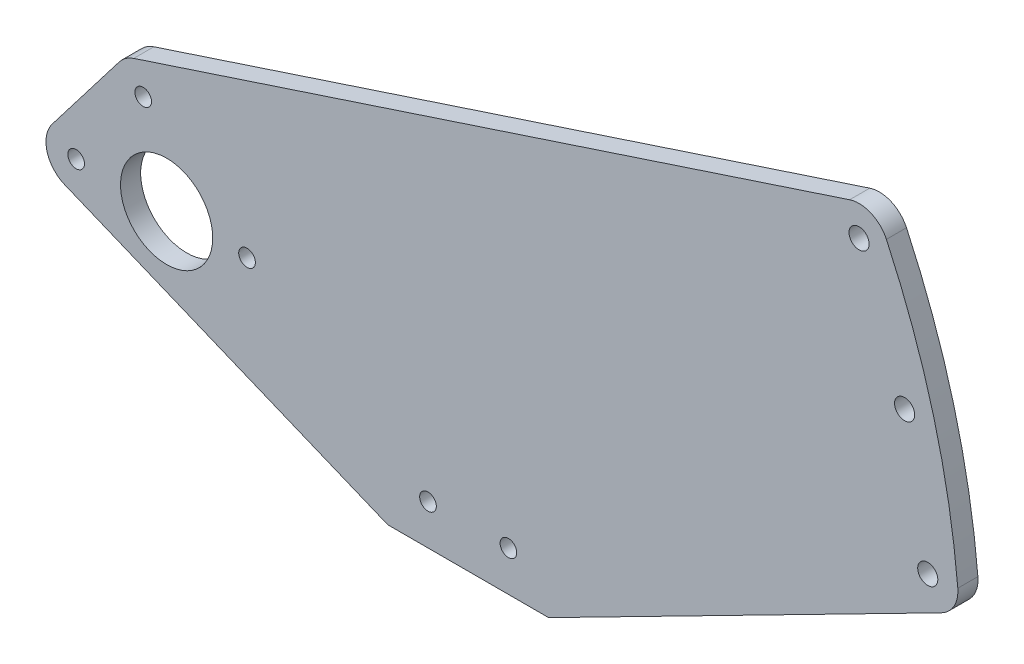
SolidWorks part; units mm, degrees
material "6061-T6 (SS)"
ref_plane "Front Plane" through (0, 0, 0) normal (0, 0, 1) x (1, 0, 0)
ref_plane "Top Plane" through (0, 0, 0) normal (0, 1, 0) x (1, 0, 0)
ref_plane "Right Plane" through (0, 0, 0) normal (1, 0, 0) x (0, 0, -1)
sketch "Sketch1" plane through (0, 0, 0) normal (0, 0, 1) x (1, 0, 0)
  line L0 (0, 0) -> (-28.575, 0) construction
  line L1 (0, 0) -> (-7.3958, 27.6013) construction
  line L2 (0, 0) -> (240.3818, 21.0307) construction
  line L3 (0, 0) -> (25.4, 0) construction
  line L4 (0, 0) -> (240.3818, 21.0307) construction
  line L5 (0, 0) -> (233.0779, 62.453) construction
  line L6 (-36.1317, 5.7985) -> (-14.9524, 33.3998)
  line L7 (-32.1995, -8.8084) -> (69.85, -50.8)
  line L8 (-10.3723, 36.6493) -> (215.7155, 111.0258)
  line L10 (0, 0) -> (0, -38.1) construction
  line L11 (0, -38.1) -> (233.0779, -38.1) construction
  line L12 (82.55, -38.1) -> (107.95, -38.1) construction
  line L13 (69.85, -50.8) -> (120.65, -50.8)
  line L14 (120.65, -50.8) -> (244.7133, 12.5476)
  circle A0 centre (0, 0) radius 14.5542
  circle A1 centre (-28.575, 0) radius 2.6289
  circle A2 centre (-7.3958, 27.6013) radius 2.6289
  circle A3 centre (240.3818, 21.0307) radius 3.175
  circle A4 centre (233.0779, 62.453) radius 3.175
  circle A5 centre (218.6921, 101.9778) radius 3.175
  arc A7 (-32.1995, -8.8084) -> (-36.1317, 5.7985) centre (-28.575, 0) cw
  arc A8 (-10.3723, 36.6493) -> (-14.9524, 33.3998) centre (-7.3958, 27.6013) ccw
  arc A9 (227.3247, 106.0032) -> (215.7155, 111.0258) centre (218.6921, 101.9778) ccw
  arc A10 (227.3247, 106.0032) -> (249.8705, 21.8608) centre (0, 0) cw
  arc A11 (249.8705, 21.8608) -> (244.7133, 12.5476) centre (240.3818, 21.0307) cw
  circle A12 centre (82.55, -38.1) radius 2.6289
  circle A13 centre (107.95, -38.1) radius 2.6289
  circle A14 centre (25.4, 0) radius 2.6289
  dimension "D1" = 29.1084
  dimension "D3" = 5.2578
  dimension "D6" = 5.2578
  dimension "D9" = 6.35
  dimension "D12" = 9.525
  dimension "D13" = 9.525
  dimension "D14" = 12.7
  dimension "D15" = 9.525
  dimension "D17" = 5.2578
  dimension "D18" = 5.2578
  dimension "D19" = 82.55
  dimension "D20" = 25.4
  dimension "D22" = 12.7
  dimension "D24" = 5.2578
  dimension "D2" = 28.575
  dimension "D4" = 75
  dimension "D5" = 28.575
  dimension "D7" = 5
  dimension "D8" = 241.3
  dimension "D11" = 10
  dimension "D16" = 38.1
  dimension "D21" = 12.7
  dimension "D23" = 25.4
  dimension "D10" = 3
extrude "Boss-Extrude1" add sketch "Sketch1" along normal blind 6.35
